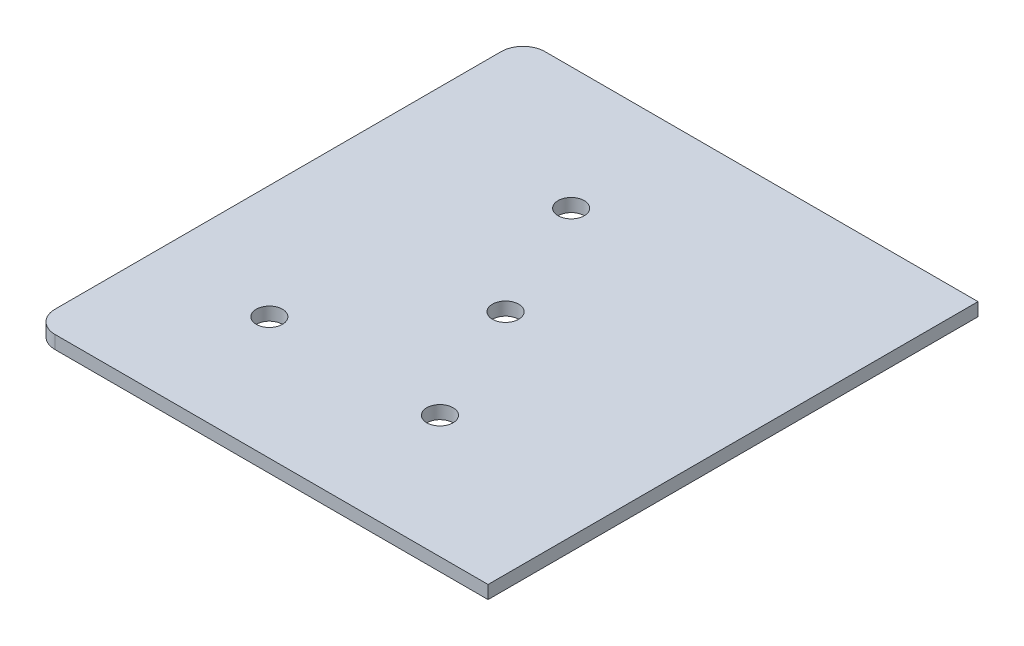
SolidWorks part; units mm, degrees
material "Oak"
ref_plane "Front Plane" through (0, 0, 0) normal (0, 0, 1) x (1, 0, 0)
ref_plane "Top Plane" through (0, 0, 0) normal (0, 1, 0) x (1, 0, 0)
ref_plane "Right Plane" through (0, 0, 0) normal (1, 0, 0) x (0, 0, -1)
sketch "Sketch1" plane through (0, 0, 0) normal (0, 1, 0) x (1, 0, 0)
  line L0 (558.8, 99.2707) -> (461.5124, 17.6367)
  line L1 (-558.8, -177.8) -> (558.8, -177.8)
  line L2 (-558.8, 177.8) -> (558.8, 177.8)
  line L3 (558.8, -177.8) -> (558.8, 177.8)
  line L4 (-558.8, -177.8) -> (558.8, 177.8) construction
  line L5 (-558.8, 177.8) -> (558.8, -177.8) construction
  line L6 (-228.6, 177.8) -> (228.6, 177.8)
  line L7 (-228.6, -177.8) -> (228.6, -177.8)
  line L8 (228.6, 177.8) -> (228.6, -177.8)
  line L9 (-228.6, 177.8) -> (228.6, -177.8) construction
  line L10 (-228.6, -177.8) -> (228.6, 177.8) construction
  line L11 (228.6, -177.8) -> (558.8, 99.2707)
  line L12 (-228.6, 177.8) -> (-228.6, -177.8)
  point P4 (0, 0)
extrude "Boss-Extrude1" add sketch "Sketch1" along normal blind 9.525 contours L8 L11 L0 L3 L2 region at (358.5765, 0, -54.5316)
extrude "Boss-Extrude2" add sketch "Sketch1<4>" along normal blind 9.525 contours L11 L1 L3 L0 region at (448.7333, 0, 85.4431)
sketch "Sketch1<4>" plane through (0, 0, 0) normal (0, 1, 0) x (1, 0, 0) same geometry as "Sketch1"
sketch "Sketch3" plane through (0, 0, 0) normal (0, -1, 0) x (1, 0, 0)
  line L0 (558.8, 177.8) -> (228.6, -177.8)
  line L1 (228.6, 177.8) -> (558.8, -177.8)
  line L2 (228.6, -177.8) -> (393.7, -177.8)
  line L3 (228.6, -177.8) -> (558.8, -177.8) construction
  line L4 (393.7, 0) -> (393.7, -177.8)
  line L5 (393.7, 0) -> (228.6, 0)
  line L6 (228.6, -177.8) -> (228.6, 177.8) construction
  line L7 (393.7, 0) -> (558.8, 0)
  line L8 (228.6, 0) -> (228.6, 177.8)
  line L9 (558.8, 177.8) -> (558.8, -177.8) construction
  line L10 (311.15, 44.45) -> (311.15, 0)
  line L15 (311.15, -88.9) -> (393.7, -88.9)
  line L18 (476.25, 88.9) -> (311.15, 88.9)
  line L19 (311.15, 88.9) -> (311.15, 44.45)
  line L25 (228.6, 177.8) -> (558.8, 177.8) construction
  line L33 (311.15, -177.8) -> (476.25, 177.8)
  circle A0 centre (393.7, 0) radius 9.525
  circle A1 centre (311.15, 88.9) radius 9.525
  circle A2 centre (434.975, 88.9) radius 9.525
  circle A3 centre (352.425, -88.9) radius 9.525
  dimension "D1" = 162.026
  dimension "D2" = 137.121
  dimension "D3" = 137.121
  dimension "D4" = 98.0145
  dimension "D5" = 65.095
extrude "Cut-Extrude6" cut sketch "Sketch3" along direction (0, 1, 0) on the side against the normal through all contours L33 A2 L18 | L18 A2 L33 | L33 A2 L18 | L18 A2 L33 | L19 A1 L1 | L1 A1 L18 | L18 A1 L1 | L1 A1 L19 | L1 A0 L0 | L0 A0 L33 | L33 A0 L1 | L1 A0 L5 | L5 A0 L0 | L0 A0 L33 | L33 A0 L1 | L33 A3 L15 | L15 A3 L33 | L33 A3 L15 | L15 A3 L33 | L1 A0 L7 | L33 A0 L4 region at (388.042, 0, -2.4673) region at (390.1736, 0, -5.2495) region at (349.5531, 0, -84.4003) region at (347.3556, 0, -92.1355) region at (397.2264, 0, 5.2495) region at (388.042, 0, 2.4673) region at (399.358, 0, -2.4673) region at (395.9673, 0, -5.7736) region at (399.358, 0, 2.4673) region at (392.3415, 0, -6.1519) region at (392.7649, 0, 5.9126) region at (357.4944, 0, -85.6645) region at (355.2969, 0, -93.3997) region at (313.4173, 0, 83.1264) region at (316.808, 0, 86.4327) region at (429.9056, 0, 85.6645) region at (437.8469, 0, 84.4003) region at (440.0444, 0, 92.1355) region at (306.5523, 0, 87.0945) region at (313.1564, 0, 93.5011) region at (432.1031, 0, 93.3997)
fillet "Fillet1" radius 15.875 2 edges at (228.6, 4.7625, 177.8) (228.6, 4.7625, -177.8)
